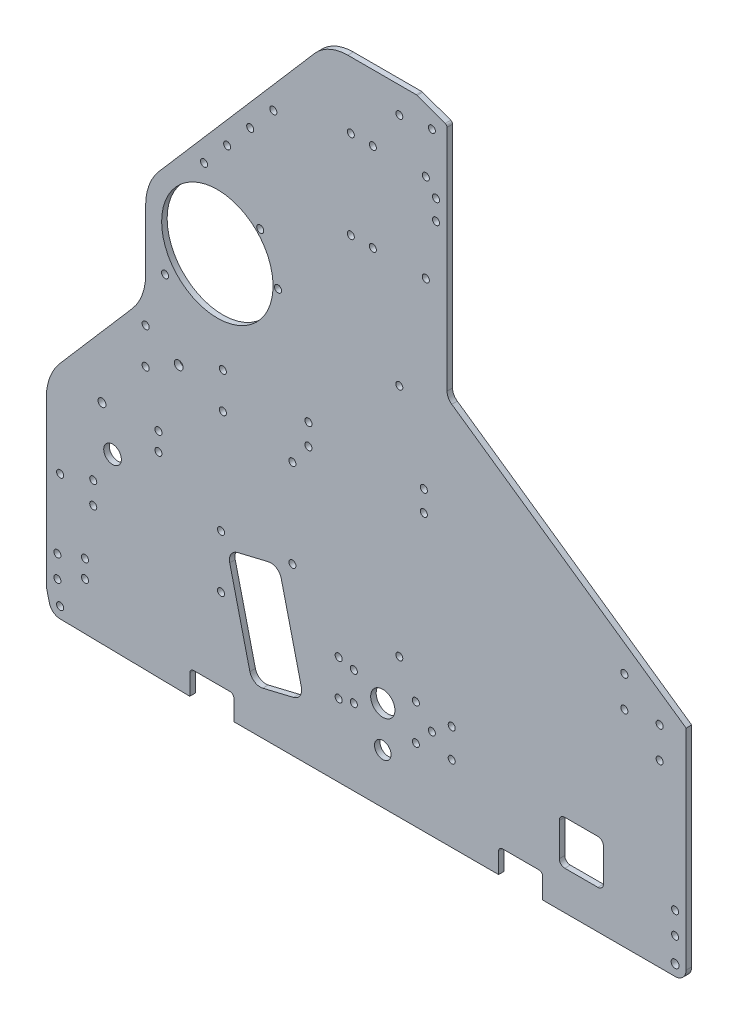
SolidWorks part; units mm, degrees
ref_plane "Front Plane" through (0, 0, 0) normal (0, 0, 1) x (1, 0, 0)
ref_plane "Top Plane" through (0, 0, 0) normal (0, 1, 0) x (1, 0, 0)
ref_plane "Right Plane" through (0, 0, 0) normal (1, 0, 0) x (0, 0, -1)
sketch "Sketch1" plane through (0, 0, 0) normal (0, 0, 1) x (1, 0, 0)
  line L0 (82.55, -20.32) -> (82.55, -6.35)
  line L2 (0, 0) -> (0, 157.48)
  line L4 (368.3, -20.32) -> (368.3, 106.68)
  line L5 (82.55, -6.35) -> (107.95, -6.35)
  line L6 (107.95, -6.35) -> (107.95, -20.32)
  line L7 (107.95, -20.32) -> (260.35, -20.32)
  line L8 (260.35, -20.32) -> (260.35, -6.35)
  line L9 (260.35, -6.35) -> (285.75, -6.35)
  line L10 (285.75, -6.35) -> (285.75, -20.32)
  line L11 (285.75, -20.32) -> (368.3, -20.32)
  line L12 (361.95, 12.7) -> (368.3, 12.7) construction
  line L13 (0, 0) -> (6.35, 0) construction
  line L14 (0.1896, -7.8901) -> (1.7771, -14.2401)
  line L15 (7.8295, -19.0491) -> (82.55, -20.32)
  line L16 (0, 0) -> (0, -6.35)
  line L17 (76.2, 141.605) -> (79.375, 141.605) construction
  line L18 (57.15, 131.2863) -> (101.6, 131.2862) construction
  line L19 (57.15, 131.2863) -> (57.15, 151.9238) construction
  line L20 (101.6, 131.2862) -> (101.6, 151.9237) construction
  line L21 (57.15, 151.9238) -> (101.6, 151.9237) construction
  line L22 (57.15, 131.2863) -> (101.6, 151.9237) construction
  line L23 (101.6, 131.2862) -> (57.15, 151.9238) construction
  line L25 (203.2, 59.805) -> (203.2, 194.805) construction
  line L26 (203.2, 194.805) -> (203.2, 329.805) construction
  line L27 (355.6, 332.105) -> (330.2, 332.105) construction
  line L28 (330.2, 332.105) -> (330.2, 217.805) construction
  line L29 (330.2, 217.805) -> (355.6, 217.805) construction
  line L30 (355.6, 217.805) -> (355.6, 332.105) construction
  line L31 (203.2, 344.805) -> (203.2, 194.805) construction
  line L32 (50.8, 332.105) -> (76.2, 332.105) construction
  line L33 (76.2, 332.105) -> (76.2, 217.805) construction
  line L34 (50.8, 217.805) -> (50.8, 332.105) construction
  line L35 (76.2, 217.805) -> (50.8, 217.805) construction
  line L36 (213.2, 344.805) -> (230.6638, 338.455)
  line L37 (203.2, 344.805) -> (161.925, 344.805)
  line L38 (203.2, 344.805) -> (213.2, 344.805)
  line L39 (348.5362, 344.805) -> (413.4623, 344.805)
  line L40 (348.5362, 344.805) -> (230.6638, 344.805) construction
  line L42 (161.925, 344.805) -> (0, 157.48)
  line L44 (230.6638, 338.455) -> (230.6638, 202.565)
  line L45 (230.6638, 202.565) -> (368.3, 106.68)
  line L46 (213.2, 344.805) -> (-141.0713, 344.805) construction
  circle A0 centre (6.35, 0) radius 2.032
  circle A1 centre (6.35, 12.7) radius 2.032
  circle A2 centre (361.95, 0) radius 2.032
  circle A3 centre (361.95, 12.7) radius 2.032
  arc A5 (1.7771, -14.2401) -> (7.8295, -19.0491) centre (7.9375, -12.7) ccw
  circle A6 centre (7.9375, -12.7) radius 2.032
  arc A7 (0, -6.35) -> (0.1896, -7.8901) centre (6.35, -6.35) ccw
  circle A8 centre (38.1, 78.105) radius 5.08
  circle A9 centre (76.2, 141.605) radius 2.54
  circle A10 centre (101.6, 131.2862) radius 2.032
  circle A11 centre (101.6, 151.9237) radius 2.032
  circle A12 centre (57.15, 151.9238) radius 2.032
  circle A13 centre (57.15, 131.2863) radius 2.032
  circle A15 centre (203.2, 59.805) radius 2
  circle A16 centre (203.2, 194.805) radius 2
  circle A17 centre (203.2, 329.805) radius 2
  circle A18 centre (63.5, 313.055) radius 2.032
  circle A20 centre (355.6, 332.105) radius 2.032
  circle A21 centre (330.2, 332.105) radius 2.032
  circle A22 centre (355.6, 217.805) radius 2.032
  circle A23 centre (330.2, 217.805) radius 2.032
  circle A24 centre (50.8, 332.105) radius 2.032
  circle A25 centre (76.2, 332.105) radius 2.032
  circle A26 centre (50.8, 217.805) radius 2.032
  circle A27 centre (76.2, 217.805) radius 2.032
  circle A28 centre (221.9319, 332.105) radius 2
  circle A29 centre (224.3138, 298.831) radius 2.032
  circle A30 centre (353.06, 100.7351) radius 2.032
  circle A31 centre (332.74, 115.9751) radius 2.032
  circle A32 centre (332.74, 98.1951) radius 2.032
  circle A33 centre (353.06, 82.9551) radius 2.032
  circle A34 centre (117.3562, 280.4276) radius 2.032
  circle A35 centre (104.0678, 265.0548) radius 2.032
  circle A36 centre (90.7795, 249.682) radius 2.032
  circle A38 centre (130.6445, 295.8004) radius 2.032
  circle A39 centre (68.326, 182.9237) radius 2.032
  circle A40 centre (224.3138, 287.401) radius 2.032
  point P82 (203.2, 344.805)
  point P83 (221.9319, 341.63)
  point P90 (368.3, 62.484)
  dimension "D6" = 4.064
  dimension "D10" = 6.35
  dimension "D11" = 4.064
  dimension "D17" = 38.1
  dimension "D27" = 4
  dimension "D31" = 4.064
  dimension "D32" = 41.275
  dimension "D36" = 4.064
  dimension "D47" = 39.624
  dimension "D48" = 4.064
  dimension "D25" = 5.08
  dimension "D26" = 4.064
  dimension "D52" = 4.064
  dimension "D65" = 4.064
  dimension "D69" = 10.16
  dimension "D2" = 127
  dimension "D3" = 13.97
  dimension "D4" = 25.4
  dimension "D5" = 152.4
  dimension "D7" = 12.7
  dimension "D8" = 6.35
  dimension "D9" = 20.32
  dimension "D12" = 12.7
  dimension "D13" = 1.5875
  dimension "D14" = 82.55
  dimension "D15" = 368.3
  dimension "D16" = 6.35
  dimension "D18" = 98.425
  dimension "D19" = 38.1
  dimension "D20" = 63.5
  dimension "D21" = 3.175
  dimension "D22" = 270
  dimension "D23" = 20.6375
  dimension "D24" = 44.45
  dimension "D28" = 135
  dimension "D29" = 12.7
  dimension "D30" = 15
  dimension "D33" = 63.5
  dimension "D34" = 27.4638
  dimension "D35" = 12.7
  dimension "D37" = 114.3
  dimension "D38" = 25.4
  dimension "D39" = 12.7
  dimension "D40" = 157.48
  dimension "D41" = 142.24
  dimension "D42" = 365.125
  dimension "D43" = 10
  dimension "D44" = 6.35
  dimension "D45" = 31.75
  dimension "D46" = 6.35
  dimension "D49" = 6.35
  dimension "D50" = 203.2
  dimension "D51" = 15.24
  dimension "D53" = 17.78
  dimension "D54" = 17.78
  dimension "D55" = 20.32
  dimension "D56" = 15.24
  dimension "D57" = 92.202
  dimension "D58" = 8.382
  dimension "D59" = 20.32
  dimension "D60" = 20.32
  dimension "D61" = 8.382
  dimension "D62" = 20.32
  dimension "D63" = 8.382
  dimension "D64" = 8.382
  dimension "D66" = 35.052
  dimension "D67" = 68.326
  dimension "D68" = 11.43
extrude "Boss-Extrude1" add sketch "Sketch1" along normal blind 3.175 contours L16 A7 L14 A5 L15 L2 A0 A1 A6 region at (171.4477, 119.555, 0)
fillet "Fillet1" radius 2.286 4 edges at (285.75, -6.35, 1.5875) (107.95, -6.35, 1.5875) (260.35, -6.35, 1.5875) (82.55, -6.35, 1.5875)
fillet "Fillet2" radius 6.35 1 edges at (230.6638, 202.565, 1.5875)
sketch "Sketch2" plane through (0, 0, 0) normal (0, 0, -1) x (-1, 0, 0)
  circle A0 centre (-100.5528, 71.086) radius 2.032 construction
  circle A1 centre (-100.5528, 40.606) radius 2.032 construction
  circle A2 centre (-22.225, 18.2025) radius 2.032 construction
  circle A3 centre (-22.225, 8.0425) radius 2.032 construction
  circle A4 centre (-100.5528, 71.086) radius 2.032
  circle A5 centre (-100.5528, 40.606) radius 2.032
  circle A6 centre (-22.225, 18.2025) radius 2.032
  circle A7 centre (-22.225, 8.0425) radius 2.032
extrude "Cut-Extrude1" cut sketch "Sketch2" against normal through all
fillet "Fillet3" radius 1.5875 2 edges at (230.6638, 338.455, 1.5875) (213.2, 344.805, 1.5875)
sketch "Sketch3" plane through (0, 0, 3.175) normal (0, 0, 1) x (1, 0, 0)
  line L0 (132.9524, 63.2646) -> (132.7215, 64.2281) construction
  line L1 (128.3814, 66.8897) -> (110.6828, 62.6472) construction
  line L2 (114.5132, 58.4237) -> (126.8822, 61.3887) construction
  line L3 (108.0212, 58.3071) -> (108.2522, 57.3436) construction
  line L4 (131.2006, 57.703) -> (140.0164, 20.9265) construction
  line L5 (144.0993, 16.7636) -> (132.9524, 63.2646) construction
  line L6 (108.2522, 57.3436) -> (119.3991, 10.8426) construction
  line L7 (121.1509, 16.4042) -> (112.3351, 53.1807) construction
  line L8 (119.3991, 10.8426) -> (119.6301, 9.8791) construction
  line L9 (144.3303, 15.8001) -> (144.0993, 16.7636) construction
  line L10 (137.8383, 15.6835) -> (125.4694, 12.7185) construction
  line L11 (123.9701, 7.2175) -> (141.6687, 11.4601) construction
  line L12 (132.9524, 63.2646) -> (132.7215, 64.2281)
  line L13 (128.3814, 66.8897) -> (110.6828, 62.6472)
  line L14 (114.5132, 58.4237) -> (126.8822, 61.3887)
  line L15 (108.0212, 58.3071) -> (108.2522, 57.3436)
  line L16 (131.2006, 57.703) -> (140.0164, 20.9265)
  line L17 (144.0993, 16.7636) -> (132.9524, 63.2646)
  line L18 (108.2522, 57.3436) -> (119.3991, 10.8426)
  line L19 (121.1509, 16.4042) -> (112.3351, 53.1807)
  line L20 (119.3991, 10.8426) -> (119.6301, 9.8791)
  line L21 (144.3303, 15.8001) -> (144.0993, 16.7636)
  line L22 (137.8383, 15.6835) -> (125.4694, 12.7185)
  line L23 (123.9701, 7.2175) -> (141.6687, 11.4601)
  line L24 (127.7894, 69.3598) -> (110.0908, 65.1172)
  line L25 (105.5512, 57.715) -> (105.7822, 56.7515)
  line L26 (105.7822, 56.7515) -> (116.9291, 10.2505)
  line L27 (116.9291, 10.2505) -> (117.16, 9.287)
  line L28 (124.5622, 4.7475) -> (142.2608, 8.99)
  line L29 (146.8003, 16.3922) -> (146.5694, 17.3557)
  line L30 (146.5694, 17.3557) -> (135.4225, 63.8567)
  line L31 (135.4225, 63.8567) -> (135.1915, 64.8202)
  line L32 (14.605, -0.1369) -> (103.7278, 32.3011) construction
  line L33 (14.605, -0.1369) -> (103.7278, 32.3011)
  line L34 (0, -6.35) -> (0, 157.48) construction
  line L35 (-39.6666, 74.7152) -> (103.7278, 126.9065) construction
  line L36 (26.9875, 46.9531) -> (26.9875, 59.6531) construction
  line L37 (107.95, -20.32) -> (260.35, -20.32) construction
  line L38 (64.5259, 92.5258) -> (64.5259, 102.9405) construction
  arc A0 (132.7215, 64.2281) -> (128.6308, 66.9403) centre (129.2206, 63.3889) ccw construction
  arc A1 (110.6828, 62.6472) -> (110.4377, 62.5791) centre (111.522, 59.1463) ccw construction
  arc A2 (128.6308, 66.9403) -> (128.3814, 66.8897) centre (129.2206, 63.3889) ccw construction
  arc A3 (110.4377, 62.5791) -> (108.0212, 58.3071) centre (111.522, 59.1463) ccw construction
  arc A4 (119.6301, 9.8791) -> (123.7207, 7.1669) centre (123.1309, 10.7183) ccw construction
  arc A5 (141.9139, 11.5281) -> (144.3303, 15.8001) centre (140.8295, 14.9609) ccw construction
  arc A6 (141.6687, 11.4601) -> (141.9139, 11.5281) centre (140.8295, 14.9609) ccw construction
  arc A7 (123.7207, 7.1669) -> (123.9701, 7.2175) centre (123.1309, 10.7183) ccw construction
  arc A8 (132.7215, 64.2281) -> (128.6308, 66.9403) centre (129.2206, 63.3889) ccw
  arc A9 (110.6828, 62.6472) -> (110.4377, 62.5791) centre (111.522, 59.1463) ccw
  arc A10 (128.6308, 66.9403) -> (128.3814, 66.8897) centre (129.2206, 63.3889) ccw
  arc A11 (110.4377, 62.5791) -> (108.0212, 58.3071) centre (111.522, 59.1463) ccw
  arc A12 (119.6301, 9.8791) -> (123.7207, 7.1669) centre (123.1309, 10.7183) ccw
  arc A13 (141.9139, 11.5281) -> (144.3303, 15.8001) centre (140.8295, 14.9609) ccw
  arc A14 (141.6687, 11.4601) -> (141.9139, 11.5281) centre (140.8295, 14.9609) ccw
  arc A15 (123.7207, 7.1669) -> (123.9701, 7.2175) centre (123.1309, 10.7183) ccw
  arc A16 (110.0908, 65.1172) -> (109.6726, 65.0012) centre (111.522, 59.1463) ccw
  arc A17 (109.6726, 65.0012) -> (105.5512, 57.715) centre (111.522, 59.1463) ccw
  arc A18 (117.16, 9.287) -> (124.1369, 4.6613) centre (123.1309, 10.7183) ccw
  arc A19 (124.1369, 4.6613) -> (124.5622, 4.7475) centre (123.1309, 10.7183) ccw
  arc A20 (142.2608, 8.99) -> (142.6789, 9.1061) centre (140.8295, 14.9609) ccw
  arc A21 (142.6789, 9.1061) -> (146.8003, 16.3922) centre (140.8295, 14.9609) ccw
  arc A22 (135.1915, 64.8202) -> (128.2147, 69.446) centre (129.2206, 63.3889) ccw
  arc A23 (128.2147, 69.446) -> (127.7894, 69.3598) centre (129.2206, 63.3889) ccw
  circle A26 centre (133.35, 208.2281) radius 2.032 construction
  circle A33 centre (26.9875, 46.9531) radius 2.032
  circle A34 centre (26.9875, 59.6531) radius 2.032
  circle A35 centre (7.9375, 53.3031) radius 2.032
  circle A37 centre (32.0306, 100.8109) radius 31.75 construction
  circle A38 centre (32.0306, 100.8109) radius 2.286
  circle A39 centre (123.1207, 232.9238) radius 2.032 construction
  circle A40 centre (64.5259, 102.9405) radius 2.032
  circle A41 centre (64.5259, 92.5258) radius 2.032
  circle A42 centre (133.35, 208.2281) radius 2.032
  circle A43 centre (123.1207, 232.9238) radius 2.032
  ellipse E0 centre (124.5974, 48.8487) end of major axis (128.5376, 61.3578) minor radius 6 (131.2006, 57.703) -> (126.8822, 61.3887) ccw construction
  ellipse E1 centre (122.2349, 48.2824) end of major axis (113.0518, 57.6456) minor radius 6 (114.5132, 58.4237) -> (112.3351, 53.1807) ccw construction
  ellipse E2 centre (127.7541, 25.2585) end of major axis (131.6942, 37.7675) minor radius 6 (121.1509, 16.4042) -> (125.4694, 12.7185) ccw construction
  ellipse E3 centre (130.1166, 25.8248) end of major axis (139.2998, 16.4616) minor radius 6 (137.8383, 15.6835) -> (140.0164, 20.9265) ccw construction
  ellipse E4 centre (124.5974, 48.8487) end of major axis (120.6573, 36.3397) minor radius 6 (131.2006, 57.703) -> (126.8822, 61.3887) ccw
  ellipse E5 centre (122.2349, 48.2824) end of major axis (131.4181, 38.9192) minor radius 6 (114.5132, 58.4237) -> (112.3351, 53.1807) ccw
  ellipse E6 centre (127.7541, 25.2585) end of major axis (131.6942, 37.7675) minor radius 6 (121.1509, 16.4042) -> (125.4694, 12.7185) ccw
  ellipse E7 centre (130.1166, 25.8248) end of major axis (139.2998, 16.4616) minor radius 6 (137.8383, 15.6835) -> (140.0164, 20.9265) ccw
  point P93 (26.9875, 53.3031)
  point P115 (32.0306, 100.8109)
  dimension "D3" = 63.5
  dimension "D4" = 4.572
  dimension "D8" = 4.064
  dimension "D2" = 88.9
  dimension "D5" = 7.9375
  dimension "D6" = 19.05
  dimension "D7" = 73.6231
  dimension "D9" = 12.7
  dimension "D10" = 10.4147
  dimension "D11" = 37.5384
  dimension "D12" = 45.5727
  dimension "D1" = 2.54
extrude "Cut-Extrude2" cut sketch "Sketch3" against normal through all contours A22 A23 L24 A16 A17 L25 L26 L27 A18 A19 L28 A20 A21 L29 L30 L31 A15 A12 L20 L18 L15 A11 A9 L13 A10 A8 L12 L17 L21 A13 A14 L23 | A12 A15 L23 A14 A13 L21 L17 L12 A8 A10 L13 A9 A11 L15 L18 L20 E7 L22 E6 L19 E5 L14 E4 L16 | L22 E7 L16 E4 L14 E5 L19 E6 | A38 | A41 | A40 | A35 | A34 | A33 | A43 | A42 region at (137.844, 39.8506, 3.175) region at (126.1758, 37.0536, 3.175) region at (128.1544, 68.6507, 3.175) region at (32.0306, 100.8109, 3.175) region at (64.5259, 102.9405, 3.175) region at (64.5259, 92.5258, 3.175)
sketch "Sketch4" plane through (0, 0, 3.175) normal (0, 0, 1) x (1, 0, 0)
  line L0 (57.15, 151.9238) -> (101.6, 151.9237) construction
  line L1 (168.275, 21.4312) -> (212.725, 21.4312) construction
  line L2 (168.275, 21.4312) -> (168.275, 42.0687) construction
  line L3 (168.275, 42.0687) -> (212.725, 42.0687) construction
  line L4 (212.725, 21.4312) -> (212.725, 42.0687) construction
  line L5 (168.275, 21.4312) -> (212.725, 42.0687) construction
  line L6 (168.275, 42.0687) -> (212.725, 21.4312) construction
  line L7 (57.15, 131.2863) -> (57.15, 151.9238) construction
  line L8 (107.95, -20.32) -> (260.35, -20.32) construction
  line L9 (193.675, 31.75) -> (177.005, 31.75) construction
  line L10 (190.5, 31.75) -> (193.675, 31.75) construction
  line L11 (6.35, 12.7) -> (361.95, 12.7) construction
  line L12 (107.95, -6.35) -> (107.95, -20.32) construction
  line L13 (193.675, 31.75) -> (220.6625, 31.75) construction
  line L14 (177.005, 23.4569) -> (177.005, 40.0431) construction
  line L15 (213.2, 44.805) -> (193.2, 44.805) construction
  line L16 (213.2, 44.805) -> (213.2, 344.805) construction
  line L17 (213.2, 344.805) -> (193.2, 344.805) construction
  line L18 (193.2, 44.805) -> (193.2, 344.805) construction
  line L19 (213.2, 44.805) -> (193.2, 344.805) construction
  line L20 (213.2, 344.805) -> (193.2, 44.805) construction
  line L21 (226.9319, 332.105) -> (226.9319, 31.75) construction
  line L22 (237.33, 40.0431) -> (233.3612, 40.0431) construction
  line L23 (237.33, 23.4569) -> (233.3612, 23.4569) construction
  circle A0 centre (168.275, 42.0687) radius 2.032
  circle A1 centre (212.725, 42.0687) radius 2.032
  circle A2 centre (212.725, 21.4312) radius 2.032
  circle A3 centre (168.275, 21.4312) radius 2.032
  circle A4 centre (193.675, 31.75) radius 6.985
  circle A7 centre (220.6625, 31.75) radius 14.2875 construction
  circle A8 centre (193.675, 31.75) radius 12.7 construction
  circle A9 centre (177.005, 40.0431) radius 2.032
  circle A10 centre (177.005, 23.4569) radius 2.032
  circle A11 centre (237.33, 40.0431) radius 2.032 construction
  circle A12 centre (237.33, 23.4569) radius 2.032 construction
  circle A13 centre (193.675, 8.4667) radius 4.7625
  circle A14 centre (221.9319, 31.75) radius 2.032
  circle A15 centre (221.9319, 31.75) radius 5 construction
  circle A16 centre (221.9319, 332.105) radius 5 construction
  circle A17 centre (233.3612, 23.4569) radius 2.032
  circle A18 centre (233.3612, 40.0431) radius 2.032
  point P0 (190.5, 31.75)
  point P26 (203.2, 194.805)
  point P38 (177.005, 31.75)
  dimension "D1" = 4.064
  dimension "D4" = 13.97
  dimension "D7" = 9.525
  dimension "D10" = 25.4
  dimension "D11" = 28.575
  dimension "D16" = 10
  dimension "D17" = 4.064
  dimension "D18" = 10
  dimension "D2" = 52.07
  dimension "D3" = 3.175
  dimension "D5" = 82.55
  dimension "D6" = 26.9875
  dimension "D8" = 20
  dimension "D9" = 300
  dimension "D12" = 16.67
  dimension "D13" = 16.5862
  dimension "D14" = 60.325
  dimension "D15" = 23.2833
  dimension "D19" = 3.9688
extrude "Cut-Extrude3" cut sketch "Sketch4" against normal through all
sketch "Sketch5" plane through (0, 0, 0) normal (0, 0, -1) x (-1, 0, 0)
  line L0 (-57.15, 223.5947) -> (-57.15, 165.3337)
  line L1 (-161.925, 344.805) -> (-52.7201, 218.4699) construction
  line L2 (-57.15, 165.3337) -> (0, 99.219)
  line L3 (0, -6.35) -> (0, 157.48) construction
  line L5 (-50.4199, 215.8089) -> (0, 157.48) construction
  line L6 (-57.15, 223.5947) -> (0, 157.48)
  line L7 (0, 157.48) -> (0, 99.219)
  line L8 (-361.95, -13.97) -> (-368.3, -13.97) construction
  line L9 (-361.95, -13.97) -> (-361.95, -20.32) construction
  line L10 (-285.75, -20.32) -> (-368.3, -20.32) construction
  line L11 (-368.3, -20.32) -> (-368.3, 106.68) construction
  circle A0 centre (-98.425, 208.2281) radius 32.0675
  circle A2 centre (-361.95, -13.97) radius 2.286
  dimension "D3" = 64.135
  dimension "D7" = 4.572
  dimension "D1" = 38.1
  dimension "D2" = 57.15
  dimension "D4" = 41.275
  dimension "D5" = 41.275
  dimension "D6" = 6.35
extrude "Cut-Extrude5" cut sketch "Sketch5" against normal through all contours A0 | L7 L6 L0 L2 | A2 region at (28.575, 161.4068, 0) region at (98.425, 208.2281, 0)
fillet "Fillet4" radius 31.75 3 edges at (0, 99.219, 1.5875) (57.15, 165.3337, 1.5875) (57.15, 223.5947, 1.5875)
sketch "Sketch6" plane through (0, 0, 3.175) normal (0, 0, 1) x (1, 0, 0)
  line L0 (285.75, -20.32) -> (368.3, -20.32) construction
  line L1 (298.45, 27.305) -> (317.5, 27.305)
  line L2 (295.275, 24.13) -> (295.275, 5.08)
  line L3 (298.45, 1.905) -> (317.5, 1.905)
  line L4 (320.675, 24.13) -> (320.675, 5.08)
  line L5 (295.275, 27.305) -> (320.675, 1.905) construction
  line L6 (295.275, 1.905) -> (320.675, 27.305) construction
  line L7 (368.3, -20.32) -> (368.3, 106.68) construction
  arc A0 (295.275, 5.08) -> (298.45, 1.905) centre (298.45, 5.08) ccw
  arc A1 (317.5, 1.905) -> (320.675, 5.08) centre (317.5, 5.08) ccw
  arc A2 (317.5, 27.305) -> (320.675, 24.13) centre (317.5, 24.13) cw
  arc A3 (298.45, 27.305) -> (295.275, 24.13) centre (298.45, 24.13) ccw
  point P0 (307.975, 14.605)
  dimension "D2" = 3.175
  dimension "D1" = 25.4
  dimension "D3" = 22.225
  dimension "D4" = 47.625
extrude "Cut-Extrude6" cut sketch "Sketch6" against normal through all
fillet "Fillet5" radius 25.4 1 edges at (161.925, 344.805, 1.5875)
sketch "Sketch8" plane through (0, 0, 0) normal (0, 0, -1) x (-1, 0, 0)
  circle A0 centre (-187.96, 306.705) radius 2.032 construction
  arc A1 (-176.3652, 304.9998) -> (-176.3652, 308.4102) centre (-175.26, 306.705) ccw construction
  arc A2 (-219.0586, 304.7695) -> (-219.0586, 308.6405) centre (-218.44, 306.705) ccw construction
  circle A3 centre (-205.74, 306.705) radius 2.032 construction
  arc A4 (-219.0586, 253.9695) -> (-219.0586, 257.8405) centre (-218.44, 255.905) ccw construction
  circle A5 centre (-205.74, 255.905) radius 2.032 construction
  circle A6 centre (-187.96, 255.905) radius 2.032 construction
  arc A7 (-176.3652, 254.1998) -> (-176.3652, 257.6102) centre (-175.26, 255.905) ccw construction
  circle A8 centre (-187.96, 306.705) radius 2.032
  arc A9 (-176.3652, 304.9998) -> (-176.3652, 308.4102) centre (-175.26, 306.705) ccw
  arc A10 (-219.0586, 304.7695) -> (-219.0586, 308.6405) centre (-218.44, 306.705) ccw
  circle A11 centre (-205.74, 306.705) radius 2.032
  arc A12 (-219.0586, 253.9695) -> (-219.0586, 257.8405) centre (-218.44, 255.905) ccw
  circle A13 centre (-205.74, 255.905) radius 2.032
  circle A14 centre (-187.96, 255.905) radius 2.032
  arc A15 (-176.3652, 254.1998) -> (-176.3652, 257.6102) centre (-175.26, 255.905) ccw
  circle A16 centre (-218.44, 306.705) radius 2.032
  circle A17 centre (-175.26, 306.705) radius 2.032
  circle A18 centre (-175.26, 255.905) radius 2.032
  circle A19 centre (-218.44, 255.905) radius 2.032
  circle A20 centre (-218.44, 306.705) radius 3.9688
  circle A21 centre (-205.74, 306.705) radius 3.9688
  circle A22 centre (-175.26, 306.705) radius 3.9687
  circle A23 centre (-218.44, 255.905) radius 3.9688
  circle A24 centre (-205.74, 255.905) radius 3.9688
  circle A25 centre (-187.96, 255.905) radius 3.9687
  circle A26 centre (-175.26, 255.905) radius 3.9687
  circle A27 centre (-187.96, 306.705) radius 3.9687
  dimension "D1" = 7.9375
extrude "Cut-Extrude7" cut sketch "Sketch8" against normal through all contours A10 A16 | A9 A17 | A15 A18 | A12 A19 | A8 | A14 region at (175.26, 306.705, 0) region at (218.44, 306.705, 0) region at (218.44, 255.905, 0) region at (175.26, 255.905, 0)
sketch "Sketch10" plane through (0, 0, 3.175) normal (0, 0, 1) x (1, 0, 0)
  circle A4 centre (141.6425, 75.1606) radius 2.032 construction
  circle A5 centre (141.6425, 125.9606) radius 2.032 construction
  circle A6 centre (141.6425, 75.1606) radius 2.032
  circle A7 centre (141.6425, 125.9606) radius 2.032
extrude "Cut-Extrude8" cut sketch "Sketch10" against normal through all
fillet "Fillet6" radius 6.35 1 edges at (368.3, -20.32, 1.5875)
sketch "Sketch11" plane through (0, 0, 3.175) normal (0, 0, 1) x (1, 0, 0)
  ellipse E4 centre (150.8814, 138.43) end of major axis (150.8814, 140.462) minor radius 2.032
  ellipse E5 centre (150.8814, 150.495) end of major axis (150.8814, 152.527) minor radius 2.032
  ellipse E6 centre (217.3024, 150.495) end of major axis (217.3024, 152.527) minor radius 2.032
  ellipse E7 centre (217.3024, 138.43) end of major axis (217.3024, 140.462) minor radius 2.032
extrude "Cut-Extrude9" cut sketch "Sketch11" against normal through all
